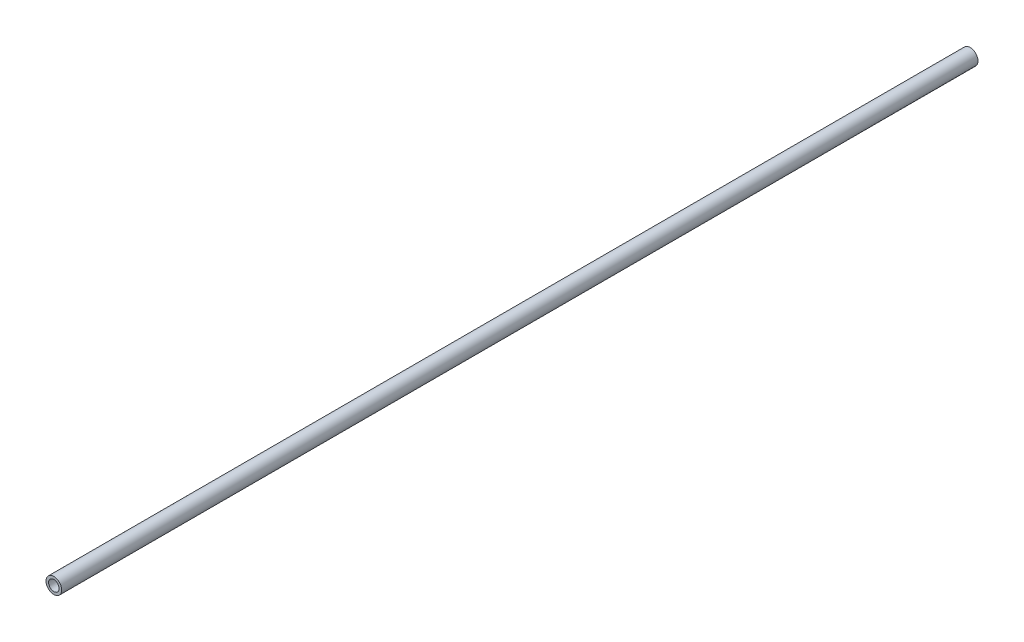
SolidWorks part; units mm, degrees
material "CarbonFiber"
ref_plane "Спереди" through (0, 0, 0) normal (0, 0, 1) x (1, 0, 0)
ref_plane "Сверху" through (0, 0, 0) normal (0, 1, 0) x (1, 0, 0)
ref_plane "Справа" through (0, 0, 0) normal (1, 0, 0) x (0, 0, -1)
sketch "Эскиз1" plane through (0, 0, 0) normal (0, 0, 1) x (1, 0, 0)
  circle A0 centre (0, 0) radius 3
  circle A1 centre (0, 0) radius 2
  dimension "D1" = 6
  dimension "D2" = 1
extrude "Бобышка-Вытянуть1" add sketch "Эскиз1" along normal mid plane 350
equation "\"D4@Fus\"=\"DFus\""
equation "\"D5@Fus\" = \"FusCentralPartLenght\""
equation "\"D8@Fus\"=\"FusTubeHeight\""
equation "\"D9@Fus\"=\"DTailTube\"+1.2"
equation "\"D3@Fus\"=\"WingOffset\""
equation "\"D19@Бобышка-Вытянуть1\" = \"CenterSectionLenght\" / 2"
equation "\"D4@FusCopy\" = \"FusTubeHeight\""
equation "\"D1@CentralPartCrossSection1\"=\"DFus\"*\"EllipseRatio\""
equation "\"D1@CentralPartCrossSection2\"=\"DFus\"*\"EllipseRatio\""
equation "\"D2@Frame\" = \"DFusTube\" + 1.2"
equation "\"DTailTube\"= 16mm'Диаметр трубки хвостового оперения"
equation "\"FusLenght\"= 700mm"
equation "\"DMotor\"= 35.2mm"
equation "\"MotorArm\"= 225mm"
equation "\"DFus\"= 140mm"
equation "\"DFusTube\"= 30mm'Диаметр трубки внутри фюзеляжа"
equation "\"FusTubeHeight\"= 40mm"
equation "\"FusCentralPartLenght\"= 350mm"
equation "\"FusNoseLenght\"= 170mm"
equation "\"WingOffset\"= 1mm'Расстояние от внутренней поверхности фюзеляжа до профиля крыла по вертикали"
equation "\"EllipseRatio\"= 0.95'Центральная часть фюзеляжа - эллипс. Этот параметр - отношение длин осей эллипса"
equation "\"FrameOffset\"= 0.6mm"
equation "\"DThreadedInsert\"= 3.6mm'Внешний диамер резьбовых втулок"
equation "\"CenterSectionLenght\"= 140mm'Длина центроплана"
equation "\"b\"= 1700mm'Размах"
equation "\"cwr\"= 236mm'Корневая хорда крыла"
equation "\"TR\"= 0.75'Сужение крыла"
equation "\"cwt\"= \"TR\" * \"cwr\"'Концевая хорда крыла"
equation "\"D3@Airfoil\"=\"cwr\""
equation "\"DWingMainSpar\"= 16mm'Диаметр главного лонжерона крыла"
equation "\"DWingSecondSpar\"= 8mm'Диаметр второго лонжерона крыла"
equation "\"WingSparsDistance\"= 80mm'Расстояния между отверстиями по лонжерон крыла"
equation "\"D7@Airfoil\"=\"DWingMainSpar\""
equation "\"D9@Airfoil\"=\"DWingSecondSpar\""
equation "\"D8@Airfoil\"=\"WingSparsDistance\"*2"
equation "\"c\"= 210mm'САХ крыла"
equation "\"FusTubeLenght\"= \"FusCentralPartLenght\" + \"FusNoseLenght\" + 10mm'Длина трубки фюзеляжа"
equation "\"bt\"=291mm'Высота лопатки хвоста"
equation "\"TailTubeLenght\"=700mm'Длина хвостовой балки"
equation "\"DStringer\"=6mm'Диаметр стрингеров"
equation "\"D1@Эскиз1\"=\"DStringer\""
equation "\"D1@Бобышка-Вытянуть1\"=\"FusCentralPartLenght\""
